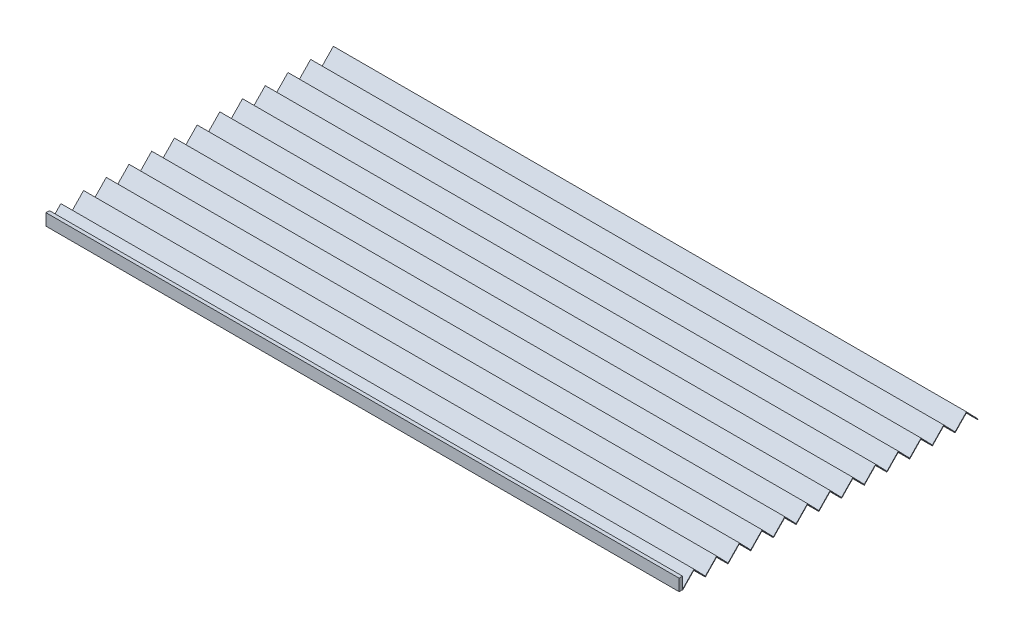
SolidWorks part; units mm, degrees
ref_plane "Front Plane" through (0, 0, 0) normal (0, 0, 1) x (1, 0, 0)
ref_plane "Top Plane" through (0, 0, 0) normal (0, 1, 0) x (1, 0, 0)
ref_plane "Right Plane" through (0, 0, 0) normal (1, 0, 0) x (0, 0, -1)
sketch "Sketch2" plane through (0, 0, 0) normal (0, 0, 1) x (1, 0, 0)
  line L1 (-270, 10) -> (270, 10)
  line L2 (-270, 10) -> (-270, 0)
  line L3 (-270, 0) -> (270, 0)
  line L4 (270, 10) -> (270, 0)
  point P4 (0, 0)
  dimension "D1" = 10
  dimension "D2" = 540
extrude "Boss-Extrude1" add sketch "Sketch2" along normal blind 3
sketch "Sketch3" plane through (270, 0, 0) normal (1, 0, 0) x (0, 0, -1)
  line L0 (0, 10) -> (251.771, 10) construction
  line L1 (0, 0) -> (251.771, 0) construction
  line L3 (0, 0) -> (9.6835, 10)
  line L4 (9.6835, 10) -> (19.367, 0)
  line L5 (19.367, 0) -> (29.0505, 10)
  line L6 (29.0505, 10) -> (38.734, 0)
  line L7 (38.734, 0) -> (48.4175, 10)
  line L8 (48.4175, 10) -> (58.101, 0)
  line L9 (58.101, 0) -> (67.7845, 10)
  line L10 (67.7845, 10) -> (77.468, 0)
  line L11 (77.468, 0) -> (87.1515, 10)
  line L12 (87.1515, 10) -> (96.835, 0)
  line L13 (96.835, 0) -> (106.5185, 10)
  line L14 (106.5185, 10) -> (116.202, 0)
  line L15 (116.202, 0) -> (125.8855, 10)
  line L16 (125.8855, 10) -> (135.569, 0)
  line L17 (135.569, 0) -> (145.2525, 10)
  line L18 (145.2525, 10) -> (154.936, 0)
  line L20 (154.936, 0) -> (164.6195, 10)
  line L21 (164.6195, 10) -> (174.303, 0)
  line L22 (174.303, 0) -> (183.9865, 10)
  line L23 (183.9865, 10) -> (193.67, 0)
  line L24 (193.67, 0) -> (203.3535, 10)
  line L25 (203.3535, 10) -> (213.037, 0)
  line L26 (213.037, 0) -> (222.7205, 10)
  line L27 (222.7205, 10) -> (232.404, 0)
  line L28 (232.404, 0) -> (242.0875, 10)
  line L29 (242.0875, 10) -> (251.771, 0)
  line L30 (251.771, 10) -> (251.771, 0) construction
  line L32 (251.771, 10) -> (251.771, 0) construction
extrude "Extrude-Thin1" add sketch "Sketch3" against normal through all thin thin type mid plane wall 0.5
